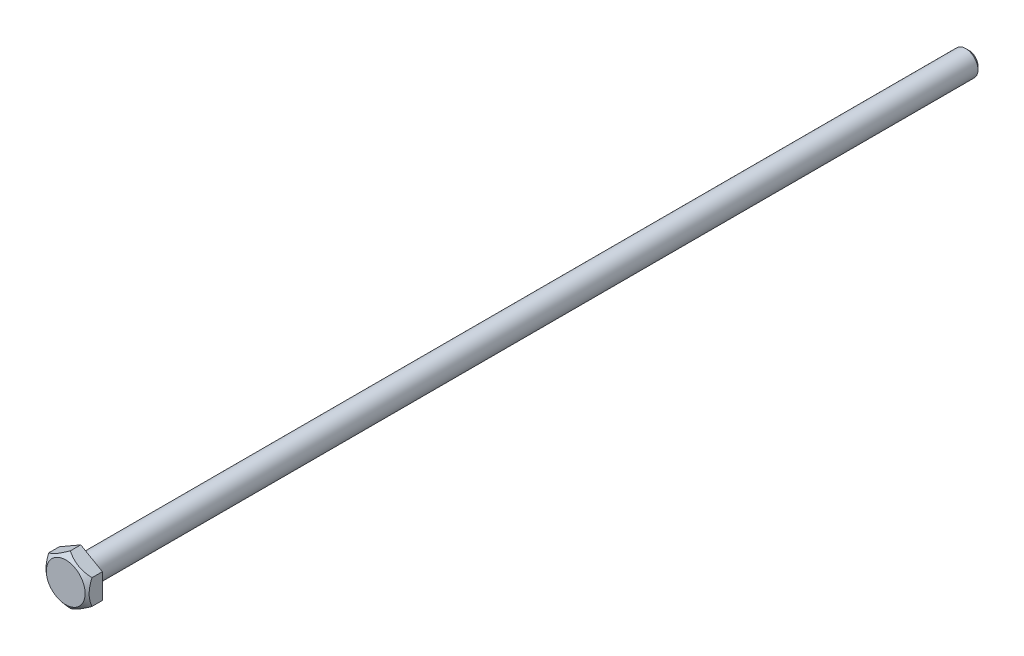
SolidWorks part; units mm, degrees
ref_plane "Front Plane" through (0, 0, 0) normal (0, 0, 1) x (1, 0, 0)
ref_plane "Top Plane" through (0, 0, 0) normal (0, 1, 0) x (1, 0, 0)
ref_plane "Right Plane" through (0, 0, 0) normal (1, 0, 0) x (0, 0, -1)
sketch "Sketch1" plane through (0, 0, 0) normal (1, 0, 0) x (0, 0, -1)
  line L0 (0, 0) -> (228.6, 0) construction
  line L1 (0, 0) -> (-3.9687, 0) construction
  line L2 (228.6, 3.175) -> (228.6, -3.175) construction
  line L3 (-3.9688, 5.5562) -> (-3.9687, -5.5563) construction
  line L4 (0, 5.5562) -> (0, -5.5562) construction
  line L5 (228.5206, 3.3125) -> (229.7906, 3.3125) construction
  line L6 (229.7906, 3.3125) -> (229.1556, 2.2126) construction
  line L7 (229.1556, 2.2126) -> (228.5206, 3.3125) construction
  line L8 (228.5603, 3.2437) -> (229.7509, 3.2437) construction
  line L9 (228.6, 3.175) -> (229.7112, 3.175) construction
  line L10 (229.0762, 2.3501) -> (229.235, 2.3501) construction
  line L11 (229.1556, 2.3501) -> (229.1556, 2.2126) construction
  line L12 (229.1556, 3.175) -> (229.1556, 3.3125) construction
  point P6 (228.6, 0)
  point P10 (-3.9687, 0)
  point P12 (0, 0)
  point P18 (224.155, -3.175)
  point P25 (229.1556, 3.2437)
  dimension "Screw Size Decimal Equivalent" = 6.35
  dimension "Head Width" = 11.1125
  dimension "Head Height" = 3.9688
  dimension "Length" = 228.6
  dimension "D1" = 60
  dimension "Thread Pitch" = 1.27
  dimension "D2" = 0.1588
  dimension "D3" = 4.445
sketch "Sketch2" plane through (0, 0, 0) normal (1, 0, 0) x (0, 0, -1)
  line L0 (228.6, 0) -> (0, 0)
  line L1 (228.6, 3.175) -> (228.6, -3.175) construction
  line L2 (0, 0) -> (0, 3.175)
  line L3 (0, 5.5562) -> (0, -5.5562) construction
  line L4 (0, 3.175) -> (227.711, 3.175)
  line L5 (227.711, 3.175) -> (228.6, 2.286)
  line L6 (228.6, 2.286) -> (228.6, 0)
  dimension "D1" = 0.889
  dimension "D2" = 45
revolve "Revolve1" add sketch "Sketch2" angle 360 about L0
sketch "Sketch3" plane through (0, 0, 0) normal (0, 0, 1) x (1, 0, 0)
  line L1 (0, 6.4158) -> (-5.5563, 3.2079)
  line L2 (-5.5563, 3.2079) -> (-5.5563, -3.2079)
  line L3 (-5.5563, -3.2079) -> (0, -6.4158)
  line L4 (0, -6.4158) -> (5.5563, -3.2079)
  line L5 (5.5563, -3.2079) -> (5.5562, 3.2079)
  line L6 (5.5562, 3.2079) -> (0, 6.4158)
  circle A0 centre (0, 0) radius 5.5562 construction
extrude "Boss-Extrude1" add sketch "Sketch3" along normal up to vertex (3.9688 mm away) up to point (0, 0, 3.9687)
sketch "Sketch4" plane through (0, 0, 3.9687) normal (0, 0, 1) x (1, 0, 0)
  circle A0 centre (0, 0) radius 5.0006
  dimension "D1" = 10.0012
extrude "Cut-Extrude1" cut sketch "Sketch4" against normal through all draft 50 flip side to cut
sketch "Sketch9" plane through (0, 0, 0) normal (0, 0, -1) x (-1, 0, 0)
  circle A0 centre (0, 0) radius 5.2784
  circle A1 centre (0, 0) radius 6.4158
  dimension "D1" = 10.5569
extrude "Cut-Extrude2" cut sketch "Sketch9" against normal blind 0.0992
sketch "Sketch5" plane through (0, 0, 0) normal (1, 0, 0) x (0, 0, -1)
  line L0 (19.4469, 3.175) -> (19.4469, -3.175) construction
  line L2 (209.1531, 3.175) -> (209.1531, -3.175) construction
  line L4 (228.6, 3.175) -> (228.6, -3.175) construction
  line L5 (0, 0) -> (228.6, 0) construction
  line L6 (0, 5.5562) -> (0, -5.5562) construction
  point P3 (19.4469, 0)
  point P6 (209.1531, 0)
  dimension "D1" = 19.4469
  dimension "D2" = 19.4469
split "Split1" [suppressed] bodies to split 112
sketch "Sketch6" [suppressed] plane through (0, 0, 0) normal (1, 0, 0) x (0, 0, -1)
  line L0 (228.5603, 3.2437) -> (229.7509, 3.2437)
  line L1 (229.7509, 3.2437) -> (229.235, 2.3501)
  line L2 (229.235, 2.3501) -> (229.0762, 2.3501)
  line L3 (229.0762, 2.3501) -> (228.5603, 3.2437)
sketch "Sketch7" [suppressed] plane through (0, 0, -228.6) normal (0, 0, -1) x (-1, 0, 0)
  circle A0 centre (0, 0) radius 3.175
curve "Helix/Spiral1" [suppressed] pitch 1.27 height 229.87 turns 181
sweep "Cut-Sweep1" [suppressed] cut profiles "Sketch6" path "Helix/Spiral1"
sketch "Sketch8" [suppressed] plane through (0, 0, 0) normal (0, 0, -1) x (-1, 0, 0)
  circle A0 centre (0, 0) radius 3.175
extrude "Boss-Extrude2" [suppressed] add sketch "Sketch8" along normal through all draft 20
equation "\"D2@Sketch1\" = \"Thread Pitch@Sketch1\" / 8"
equation "\"D3@Sketch1\" = \"Thread Pitch@Sketch1\" * 3.5"
equation "\"D1@Sketch2\" = \"Thread Pitch@Sketch1\" * .7"
equation "\"D1@Sketch4\"=\"Head Width@Sketch1\"*.9"
equation "\"D3@Helix/Spiral1\" = \"Length@Sketch1\" + \"Thread Pitch@Sketch1\""
equation "\"D4@Helix/Spiral1\" = \"Thread Pitch@Sketch1\""
equation "\"D1@Sketch5\"=\"Head Width@Sketch1\"*1.75"
equation "\"D2@Sketch5\" = \"D1@Sketch5\""
equation "\"D1@Sketch9\"=\"Head Width@Sketch1\"*.95"
equation "\"D1@Cut-Extrude2\"=\"Head Height@Sketch1\"*.025"
